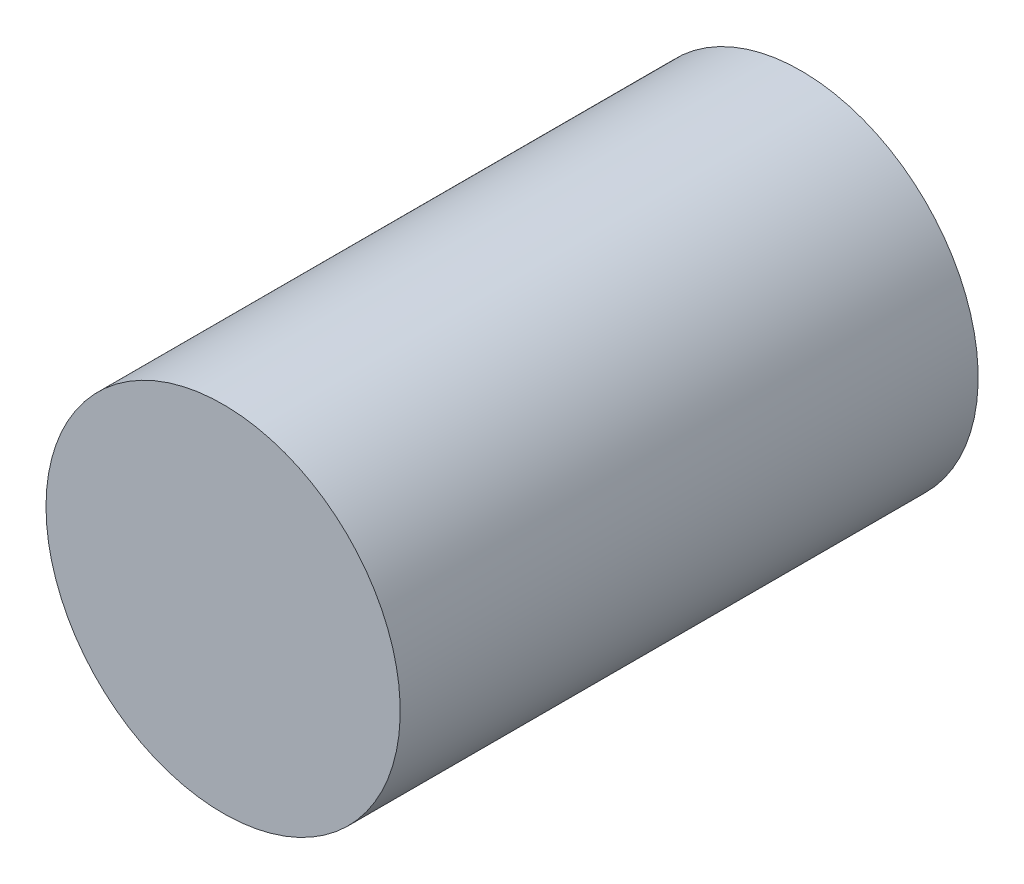
SolidWorks part; units mm, degrees
ref_plane "Front Plane" through (0, 0, 0) normal (0, 0, 1) x (1, 0, 0)
ref_plane "Top Plane" through (0, 0, 0) normal (0, 1, 0) x (1, 0, 0)
ref_plane "Right Plane" through (0, 0, 0) normal (1, 0, 0) x (0, 0, -1)
sketch "Sketch1" plane through (0, 0, 0) normal (0, 0, 1) x (1, 0, 0)
  circle A0 centre (0, 0) radius 57
extrude "Boss-Extrude1" add sketch "Sketch1" along normal blind 186 contours A0
sketch "Sketch2" plane through (0, 0, 0) normal (0, 0, -1) x (-1, 0, 0)
  circle A0 centre (0, 0) radius 31.8306
extrude "Cut-Extrude1" cut sketch "Sketch2" against normal blind 10
fillet "Fillet1" radius 10 1 edges at (-31.8306, 0, 10)
